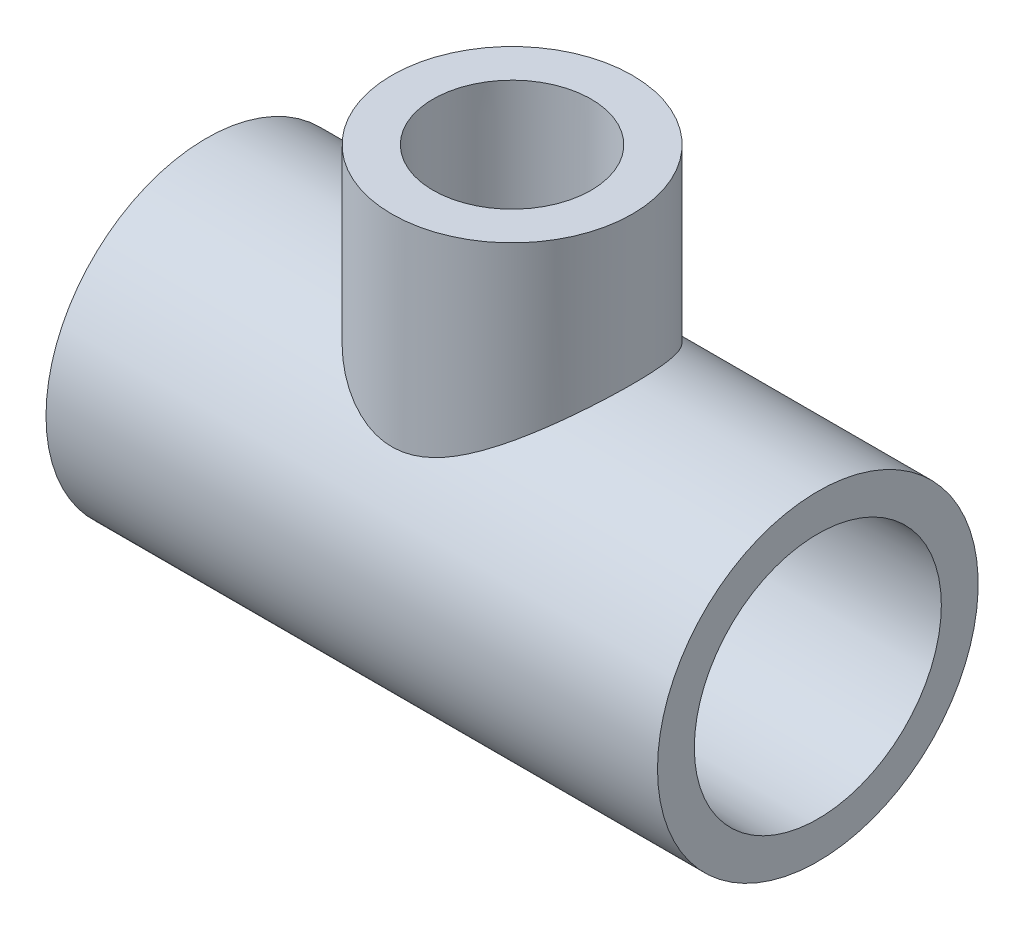
SolidWorks part; units mm, degrees
ref_plane "Front Plane" through (0, 0, 0) normal (0, 0, 1) x (1, 0, 0)
ref_plane "Top Plane" through (0, 0, 0) normal (0, 1, 0) x (1, 0, 0)
ref_plane "Right Plane" through (0, 0, 0) normal (1, 0, 0) x (0, 0, -1)
sketch "Sketch0" plane through (0, 0, 0) normal (0, 0, 1) x (1, 0, 0)
  line L0 (-41.656, 0) -> (0, 0) construction
  line L1 (0, 0) -> (0, 41.91) construction
  line L2 (-12.7, 0) -> (0, 0) construction
  line L3 (0, 0) -> (0, 19.05) construction
  line L4 (-41.656, 21.844) -> (-41.656, -21.844) construction
  line L5 (-12.7, 16.637) -> (-41.656, 16.8275) construction
  line L6 (-12.7, 16.637) -> (-12.7, -16.637) construction
  line L7 (-12.7, -16.637) -> (-41.656, -16.8275) construction
  line L8 (-41.656, 16.8275) -> (-41.656, -16.8275) construction
  line L9 (-16.383, 41.91) -> (16.383, 41.91) construction
  line L10 (-10.7696, 41.91) -> (10.7696, 41.91) construction
  line L11 (10.7696, 41.91) -> (10.6172, 19.05) construction
  line L12 (10.6172, 19.05) -> (-10.6172, 19.05) construction
  line L13 (-10.6172, 19.05) -> (-10.7696, 41.91) construction
  line L14 (-12.7, 12.1539) -> (-12.7, -12.1539) construction
  line L15 (-41.656, 0) -> (-12.7, 0) construction
  line L16 (0, 41.91) -> (0, 19.05) construction
  line L17 (0, 0) -> (12.7, 0) construction
  line L18 (-6.9342, 19.05) -> (6.9342, 19.05) construction
  line L19 (12.7, 0) -> (41.656, 0) construction
  dimension "H" = 41.656
  dimension "G" = 12.7
  dimension "M" = 43.688
  dimension "OD A" = 33.655
  dimension "OD B" = 33.274
  dimension "ID" = 24.3078
  dimension "H3" = 41.91
  dimension "G3" = 19.05
  dimension "M3" = 32.766
  dimension "OD A3" = 21.5392
  dimension "OD B3" = 21.2344
  dimension "ID3" = 13.8684
sketch "Sketch1" plane through (0, 0, 0) normal (0, 0, 1) x (1, 0, 0)
  line L0 (-41.656, 0) -> (0, 0) construction
  line L1 (-41.656, 0) -> (0, 0) construction
  line L2 (0, 0) -> (0, -21.844) construction
  line L3 (-41.656, -21.844) -> (-12.7, -21.844)
  line L4 (-41.656, -21.844) -> (-41.656, -16.8275)
  line L5 (-41.656, -16.8275) -> (-12.7, -16.637)
  line L6 (-12.7, -21.844) -> (-12.7, -16.637)
  line L7 (-12.7, -21.844) -> (0, -21.844) construction
  line L8 (41.656, -16.8275) -> (12.7, -16.637)
  line L9 (41.656, -21.844) -> (41.656, -16.8275)
  line L10 (12.7, -21.844) -> (12.7, -16.637)
  line L11 (41.656, -21.844) -> (12.7, -21.844)
revolve "Revolve1" add sketch "Sketch1" angle 360 about L1
sketch "Sketch2" plane through (0, 0, 0) normal (0, 0, 1) x (1, 0, 0)
  line L0 (10.7696, 41.91) -> (10.6172, 19.05)
  line L1 (10.6172, 19.05) -> (16.383, 19.05)
  line L2 (16.383, 19.05) -> (16.383, 41.91)
  line L3 (16.383, 41.91) -> (10.7696, 41.91)
  line L4 (0, 0) -> (0, 41.91) construction
  line L5 (0, 0) -> (0, 41.91) construction
revolve "Revolve2" add sketch "Sketch2" angle 360 about L5
sketch "Sketch3" plane through (-12.7, 0, 0) normal (1, 0, 0) x (0, 0, -1)
  circle A0 centre (0, 0) radius 12.1539
  circle A1 centre (0, 0) radius 21.844
sketch "Sketch4" plane through (-12.7, 0, 0) normal (1, 0, 0) x (0, 0, -1)
  circle A0 centre (0, 0) radius 21.844 construction
  circle A1 centre (0, 0) radius 21.844
extrude "Boss-Extrude1" add sketch "Sketch4" along normal up to vertex (25.4 mm away) up to point (12.7, 0, 0)
sketch "Sketch5" plane through (0, 19.05, 0) normal (0, -1, 0) x (1, 0, 0)
  circle A0 centre (0, 0) radius 16.383 construction
  circle A1 centre (0, 0) radius 16.383
extrude "Boss-Extrude2" add sketch "Sketch5" along normal up to vertex (19.05 mm away) up to point (0, 0, 0)
sketch "Sketch6" plane through (0, 0, 0) normal (0, 0, 1) x (1, 0, 0)
  line L0 (-41.656, -16.8275) -> (-12.7, -16.637)
  line L1 (-12.7, -16.637) -> (-12.7, -12.1539)
  line L2 (-12.7, -12.1539) -> (12.7, -12.1539)
  line L3 (12.7, -16.637) -> (12.7, 13.026) construction
  line L4 (0, -12.1539) -> (0, 0) construction
  line L5 (12.7, -16.637) -> (12.7, -12.1539)
  line L6 (41.656, -16.8275) -> (41.656, 16.8275) construction
  line L7 (41.656, -21.844) -> (41.656, 21.844) construction
  line L8 (41.656, -16.8275) -> (41.656, 0)
  line L9 (41.656, 0) -> (-41.656, 0)
  line L10 (-41.656, 0) -> (-41.656, -16.8275)
  line L11 (41.656, -16.8275) -> (12.7, -16.637)
revolve "Cut-Revolve1" cut sketch "Sketch6" angle 360 about L9
sketch "Sketch7" plane through (0, 0, 0) normal (0, 0, 1) x (1, 0, 0)
  line L0 (10.7696, 41.91) -> (10.6172, 19.05)
  line L1 (10.6172, 19.05) -> (6.9342, 19.05)
  line L2 (6.9342, 19.05) -> (6.9342, 0)
  line L3 (0, 0) -> (12.7, 0) construction
  line L4 (6.9342, 0) -> (0, 0)
  line L5 (0, 0) -> (0, 41.91)
  line L6 (-16.383, 41.91) -> (16.383, 41.91) construction
  line L7 (0, 41.91) -> (10.7696, 41.91)
revolve "Cut-Revolve2" cut sketch "Sketch7" angle 360 about L5
other "CPoint1" parameters "Diameter"=12.7, "StubLength"=19.05
ref_axis "Axis1" through (0, 29.05, 0) along (0, -1, 0)
other "CPoint2" parameters "Diameter"=25.4, "StubLength"=19.05
ref_axis "Axis2"
other "CPoint3" parameters "Diameter"=25.4, "StubLength"=19.05
ref_axis "Axis3"
other "RPoint1"
